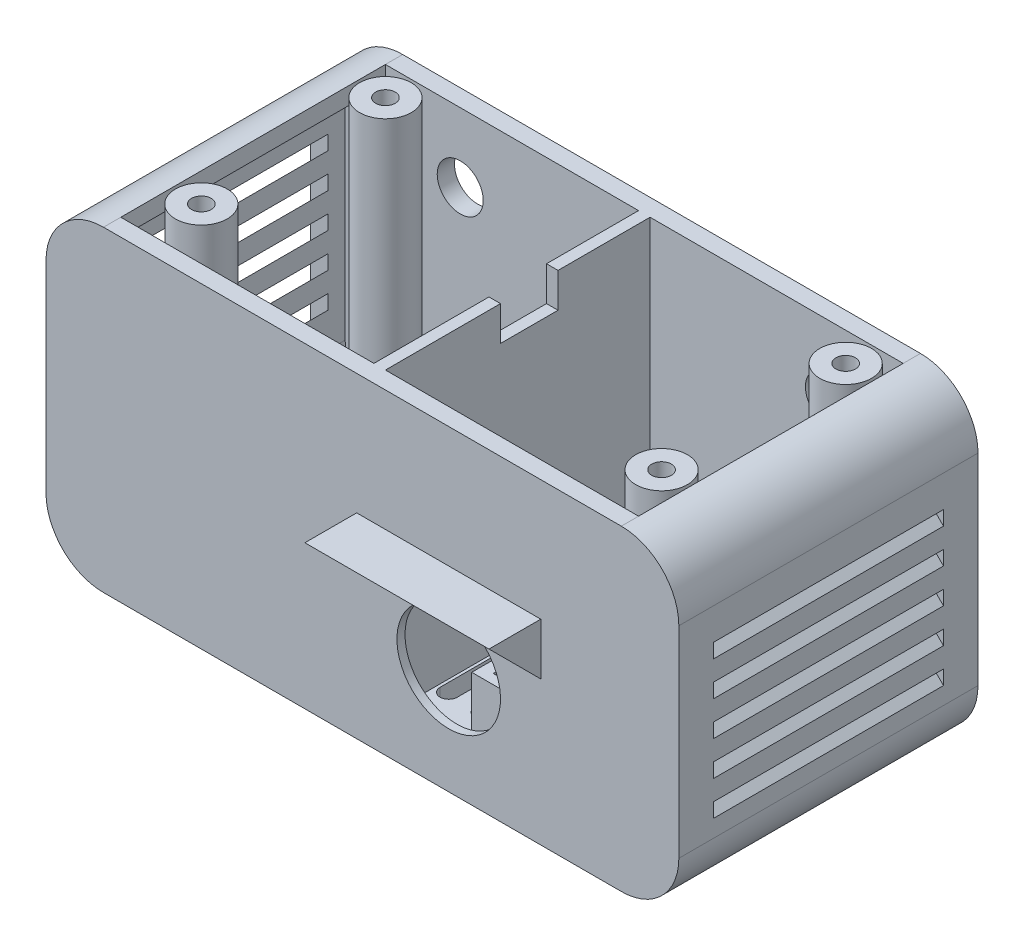
SolidWorks part; units mm, degrees
material "ABS"
ref_plane "Front Plane" through (0, 0, 0) normal (0, 0, 1) x (1, 0, 0)
ref_plane "Top Plane" through (0, 0, 0) normal (0, 1, 0) x (1, 0, 0)
ref_plane "Right Plane" through (0, 0, 0) normal (1, 0, 0) x (0, 0, -1)
sketch "Sketch1" plane through (0, 0, 0) normal (0, 0, 1) x (1, 0, 0)
  line L0 (-45, -55) -> (45, -55)
  line L1 (55, -45) -> (55, -10)
  line L2 (45, 0) -> (-45, 0)
  line L3 (-55, -10) -> (-55, -45)
  arc A0 (45, -55) -> (55, -45) centre (45, -45) ccw
  arc A1 (55, -10) -> (45, 0) centre (45, -10) ccw
  arc A2 (-45, 0) -> (-55, -10) centre (-45, -10) ccw
  arc A3 (-55, -45) -> (-45, -55) centre (-45, -45) ccw
extrude "Boss-Extrude1" add sketch "Sketch1" along normal blind 52
shell "Shell1" thickness 3 removed face at (0, 0, 26)
sketch "Sketch2" plane through (0, 0, 0) normal (0, 1, 0) x (1, 0, 0)
  circle A0 centre (-40, -8) radius 4.5
  circle A1 centre (40, -8) radius 4.5
  circle A2 centre (-40, -40) radius 4.5
  circle A3 centre (40, -40) radius 4.5
extrude "Boss-Extrude2" add sketch "Sketch2" against normal blind 52
sketch "Sketch3" plane through (0, -55, 0) normal (0, -1, 0) x (1, 0, 0)
  circle A0 centre (-40, 8) radius 3.25
  circle A1 centre (40, 8) radius 3.25
  circle A2 centre (-40, 40) radius 3.25
  circle A3 centre (40, 40) radius 3.25
extrude "Cut-Extrude1" cut sketch "Sketch3" against normal blind 49
sketch "Sketch4" plane through (0, -6, 0) normal (0, -1, 0) x (1, 0, 0)
  circle A0 centre (-40, 8) radius 1.7
  circle A1 centre (40, 8) radius 1.7
  circle A2 centre (-40, 40) radius 1.7
  circle A3 centre (40, 40) radius 1.7
extrude "Cut-Extrude2" cut sketch "Sketch4" against normal through all
ref_plane "Plane1" through (0, 0, 26) normal (0, 0, 1) x (1, 0, 0)
sketch "Sketch5" plane through (0, 0, 26) normal (0, 0, 1) x (1, 0, 0)
  line L0 (-51, -14) -> (-51, -11.5)
  line L1 (-51, -11.5) -> (-55.5, -16)
  line L2 (-55.5, -16) -> (-55.5, -18.5)
  line L3 (-55.5, -18.5) -> (-51, -14)
  line L4 (51, -14) -> (51, -11.5)
  line L5 (51, -11.5) -> (55.5, -16)
  line L6 (55.5, -16) -> (55.5, -18.5)
  line L7 (55.5, -18.5) -> (51, -14)
  line L8 (-51, -20) -> (-51, -17.5)
  line L9 (-51, -17.5) -> (-55.5, -22)
  line L10 (-55.5, -22) -> (-55.5, -24.5)
  line L11 (-55.5, -24.5) -> (-51, -20)
  line L12 (51, -20) -> (51, -17.5)
  line L13 (51, -17.5) -> (55.5, -22)
  line L14 (55.5, -22) -> (55.5, -24.5)
  line L15 (55.5, -24.5) -> (51, -20)
  line L16 (-51, -26) -> (-51, -23.5)
  line L17 (-51, -23.5) -> (-55.5, -28)
  line L18 (-55.5, -28) -> (-55.5, -30.5)
  line L19 (-55.5, -30.5) -> (-51, -26)
  line L20 (51, -26) -> (51, -23.5)
  line L21 (51, -23.5) -> (55.5, -28)
  line L22 (55.5, -28) -> (55.5, -30.5)
  line L23 (55.5, -30.5) -> (51, -26)
  line L24 (-51, -32) -> (-51, -29.5)
  line L25 (-51, -29.5) -> (-55.5, -34)
  line L26 (-55.5, -34) -> (-55.5, -36.5)
  line L27 (-55.5, -36.5) -> (-51, -32)
  line L28 (51, -32) -> (51, -29.5)
  line L29 (51, -29.5) -> (55.5, -34)
  line L30 (55.5, -34) -> (55.5, -36.5)
  line L31 (55.5, -36.5) -> (51, -32)
  line L32 (-51, -38) -> (-51, -35.5)
  line L33 (-51, -35.5) -> (-55.5, -40)
  line L34 (-55.5, -40) -> (-55.5, -42.5)
  line L35 (-55.5, -42.5) -> (-51, -38)
  line L36 (51, -38) -> (51, -35.5)
  line L37 (51, -35.5) -> (55.5, -40)
  line L38 (55.5, -40) -> (55.5, -42.5)
  line L39 (55.5, -42.5) -> (51, -38)
extrude "Cut-Extrude3" cut sketch "Sketch5" against normal blind 20 and the other way blind 20
sketch "Sketch6" plane through (0, -55, 0) normal (0, -1, 0) x (1, 0, 0)
  line L0 (-33, 12) -> (-33, 40) construction
  line L1 (-34.5, 12) -> (-34.5, 40)
  line L2 (-31.5, 12) -> (-31.5, 40)
  line L3 (-27, 12) -> (-27, 40) construction
  line L4 (-28.5, 12) -> (-28.5, 40)
  line L5 (-25.5, 12) -> (-25.5, 40)
  line L6 (-21, 12) -> (-21, 40) construction
  line L7 (-22.5, 12) -> (-22.5, 40)
  line L8 (-19.5, 12) -> (-19.5, 40)
  line L9 (-15, 12) -> (-15, 40) construction
  line L10 (-16.5, 12) -> (-16.5, 40)
  line L11 (-13.5, 12) -> (-13.5, 40)
  line L12 (-9, 12) -> (-9, 40) construction
  line L13 (-10.5, 12) -> (-10.5, 40)
  line L14 (-7.5, 12) -> (-7.5, 40)
  line L15 (-3, 12) -> (-3, 40) construction
  line L16 (-4.5, 12) -> (-4.5, 40)
  line L17 (-1.5, 12) -> (-1.5, 40)
  line L18 (3, 12) -> (3, 40) construction
  line L19 (1.5, 12) -> (1.5, 40)
  line L20 (4.5, 12) -> (4.5, 40)
  line L21 (9, 12) -> (9, 40) construction
  line L22 (7.5, 12) -> (7.5, 40)
  line L23 (10.5, 12) -> (10.5, 40)
  line L24 (21, 12) -> (21, 40) construction
  line L25 (19.5, 12) -> (19.5, 40)
  line L26 (22.5, 12) -> (22.5, 40)
  arc A0 (-34.5, 12) -> (-31.5, 12) centre (-33, 12) ccw
  arc A1 (-31.5, 40) -> (-34.5, 40) centre (-33, 40) ccw
  arc A2 (-28.5, 12) -> (-25.5, 12) centre (-27, 12) ccw
  arc A3 (-25.5, 40) -> (-28.5, 40) centre (-27, 40) ccw
  arc A4 (-22.5, 12) -> (-19.5, 12) centre (-21, 12) ccw
  arc A5 (-19.5, 40) -> (-22.5, 40) centre (-21, 40) ccw
  arc A6 (-16.5, 12) -> (-13.5, 12) centre (-15, 12) ccw
  arc A7 (-13.5, 40) -> (-16.5, 40) centre (-15, 40) ccw
  arc A8 (-10.5, 12) -> (-7.5, 12) centre (-9, 12) ccw
  arc A9 (-7.5, 40) -> (-10.5, 40) centre (-9, 40) ccw
  arc A10 (-4.5, 12) -> (-1.5, 12) centre (-3, 12) ccw
  arc A11 (-1.5, 40) -> (-4.5, 40) centre (-3, 40) ccw
  arc A12 (1.5, 12) -> (4.5, 12) centre (3, 12) ccw
  arc A13 (4.5, 40) -> (1.5, 40) centre (3, 40) ccw
  arc A14 (7.5, 12) -> (10.5, 12) centre (9, 12) ccw
  arc A15 (10.5, 40) -> (7.5, 40) centre (9, 40) ccw
  arc A16 (19.5, 12) -> (22.5, 12) centre (21, 12) ccw
  arc A17 (22.5, 40) -> (19.5, 40) centre (21, 40) ccw
  point P2 (-33, 26)
  point P7 (-27, 26)
  point P14 (-21, 26)
  point P21 (-15, 26)
  point P28 (-9, 26)
  point P35 (-3, 26)
  point P42 (3, 26)
  point P49 (9, 26)
  point P56 (21, 26)
extrude "Cut-Extrude4" cut sketch "Sketch6" against normal blind 3.5
sketch "Sketch7" plane through (0, 0, 0) normal (0, 0, -1) x (-1, 0, 0)
  circle A0 centre (32, -12) radius 4
  circle A1 centre (-32, -12) radius 4
extrude "Cut-Extrude5" cut sketch "Sketch7" against normal blind 3.5
sketch "Sketch8" plane through (0, 0, 0) normal (0, 1, 0) x (1, 0, 0)
  line L0 (-30.25, -26) -> (30.25, -26) construction
  line L1 (-1, -49) -> (1, -49)
  line L2 (-1, -49) -> (-1, -3)
  line L3 (-1, -3) -> (1, -3)
  line L4 (1, -49) -> (1, -3)
  line L5 (-1, -49) -> (1, -3) construction
  line L6 (-1, -3) -> (1, -49) construction
  line L7 (45, -3) -> (-45, -3) construction
  point P0 (0, -26)
extrude "Boss-Extrude3" add sketch "Sketch8" against normal blind 52
sketch "Sketch9" plane through (0, 0, 0) normal (0, 1, 0) x (1, 0, 0)
  line L1 (-2, -29) -> (2, -29)
  line L2 (-2, -29) -> (-2, -19)
  line L3 (-2, -19) -> (2, -19)
  line L4 (2, -29) -> (2, -19)
  line L5 (-2, -29) -> (2, -19) construction
  line L6 (-2, -19) -> (2, -29) construction
  point P0 (0, -24)
extrude "Cut-Extrude6" cut sketch "Sketch9" against normal blind 6
sketch "Sketch10" plane through (0, -52, 0) normal (0, 1, 0) x (1, 0, 0)
  line L0 (-30.25, -26) -> (30.25, -26) construction
  line L1 (-47, -36) -> (-41, -36)
  line L2 (-47, -36) -> (-47, -16)
  line L3 (-47, -16) -> (-41, -16)
  line L4 (-41, -36) -> (-41, -16)
  line L5 (-47, -36) -> (-41, -16) construction
  line L6 (-47, -16) -> (-41, -36) construction
  point P0 (-44, -26)
extrude "Boss-Extrude4" add sketch "Sketch10" along normal blind 8
sketch "Sketch11" plane through (0, -44, 0) normal (0, 1, 0) x (1, 0, 0)
  line L0 (-30.25, -26) -> (30.25, -26) construction
  line L1 (-44.95, -34.3) -> (-43.05, -34.3)
  line L2 (-44.95, -34.3) -> (-44.95, -17.7)
  line L3 (-44.95, -17.7) -> (-43.05, -17.7)
  line L4 (-43.05, -34.3) -> (-43.05, -17.7)
  line L5 (-44.95, -34.3) -> (-43.05, -17.7) construction
  line L6 (-44.95, -17.7) -> (-43.05, -34.3) construction
  point P0 (-44, -26)
extrude "Cut-Extrude7" cut sketch "Sketch11" against normal blind 6
sketch "Sketch12" plane through (0, -52, 0) normal (0, 1, 0) x (1, 0, 0)
  line L1 (27, -43.5) -> (33, -43.5)
  line L2 (27, -43.5) -> (27, -6.5)
  line L3 (27, -6.5) -> (33, -6.5)
  line L4 (33, -43.5) -> (33, -6.5)
  line L5 (27, -43.5) -> (33, -6.5) construction
  line L6 (27, -6.5) -> (33, -43.5) construction
  point P0 (30, -25)
extrude "Boss-Extrude5" add sketch "Sketch12" along normal blind 8
sketch "Sketch13" plane through (0, -44, 0) normal (0, 1, 0) x (1, 0, 0)
  line L1 (29.05, -41.8) -> (30.95, -41.8)
  line L2 (29.05, -41.8) -> (29.05, -8.2)
  line L3 (29.05, -8.2) -> (30.95, -8.2)
  line L4 (30.95, -41.8) -> (30.95, -8.2)
  line L5 (29.05, -41.8) -> (30.95, -8.2) construction
  line L6 (29.05, -8.2) -> (30.95, -41.8) construction
  point P0 (30, -25)
extrude "Cut-Extrude8" cut sketch "Sketch13" against normal blind 6
sketch "Sketch14" plane through (0, -44, 0) normal (0, 1, 0) x (1, 0, 0)
  line L1 (30.9, -44.5) -> (33.1, -44.5)
  line L2 (30.9, -44.5) -> (30.9, -5.5)
  line L3 (30.9, -5.5) -> (33.1, -5.5)
  line L4 (33.1, -44.5) -> (33.1, -5.5)
  line L5 (30.9, -44.5) -> (33.1, -5.5) construction
  line L6 (30.9, -5.5) -> (33.1, -44.5) construction
  point P0 (32, -25)
extrude "Cut-Extrude9" cut sketch "Sketch14" against normal blind 5
sketch "Sketch15" plane through (0, -52, 0) normal (0, 1, 0) x (1, 0, 0)
  line L1 (12, -45) -> (18, -45)
  line L2 (12, -45) -> (12, -5)
  line L3 (12, -5) -> (18, -5)
  line L4 (18, -45) -> (18, -5)
  line L5 (12, -45) -> (18, -5) construction
  line L6 (12, -5) -> (18, -45) construction
  point P0 (15, -25)
extrude "Boss-Extrude6" add sketch "Sketch15" along normal blind 10
sketch "Sketch16" plane through (0, -42, 0) normal (0, 1, 0) x (1, 0, 0)
  line L1 (14.05, -43.3) -> (15.95, -43.3)
  line L2 (14.05, -43.3) -> (14.05, -6.7)
  line L3 (14.05, -6.7) -> (15.95, -6.7)
  line L4 (15.95, -43.3) -> (15.95, -6.7)
  line L5 (14.05, -43.3) -> (15.95, -6.7) construction
  line L6 (14.05, -6.7) -> (15.95, -43.3) construction
  point P0 (15, -25)
extrude "Cut-Extrude10" cut sketch "Sketch16" against normal blind 4
sketch "Sketch17" plane through (0, 0, 52) normal (0, 0, 1) x (1, 0, 0)
  circle A0 centre (15, -36.5) radius 9
extrude "Cut-Extrude11" cut sketch "Sketch17" against normal blind 3.5
sketch "Sketch18" plane through (0, 0, 49) normal (0, 0, -1) x (-1, 0, 0)
  circle A0 centre (-15, -36.5) radius 12.7
extrude "Cut-Extrude12" cut sketch "Sketch18" against normal blind 1.6
ref_plane "Plane2" through (15, 0, 0) normal (1, 0, 0) x (0, 0, -1)
sketch "Sketch19" plane through (15, 0, 0) normal (1, 0, 0) x (0, 0, -1)
  line L0 (-51, -21) -> (-61, -21)
  line L1 (-61, -21) -> (-51, -31)
  line L2 (-51, -31) -> (-51, -21)
extrude "Boss-Extrude7" add sketch "Sketch19" along normal mid plane 32
